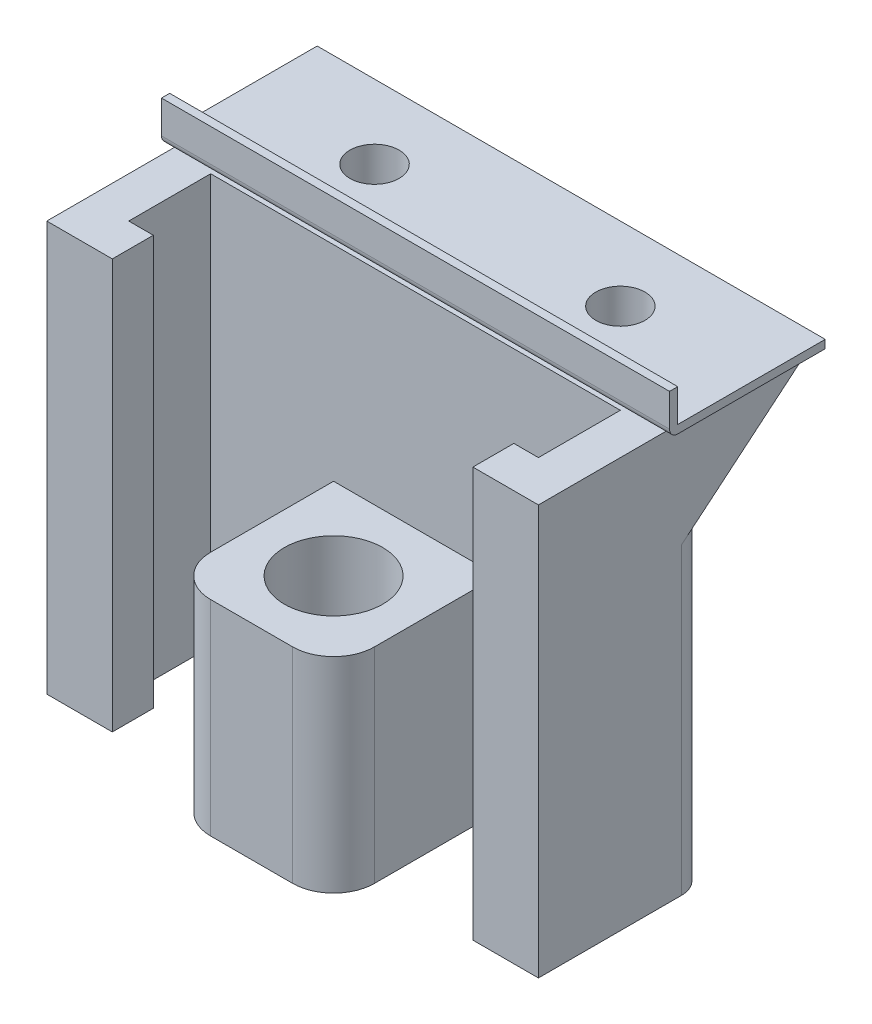
SolidWorks part; units mm, degrees
note: The reader was unsure of these and kept them because the rebuilt part matched: shared geometry of "草图9<8>".
material "1060 合金"
ref_plane "前视基准面" through (0, 0, 0) normal (0, 0, 1) x (1, 0, 0)
ref_plane "上视基准面" through (0, 0, 0) normal (0, 1, 0) x (1, 0, 0)
ref_plane "右视基准面" through (0, 0, 0) normal (1, 0, 0) x (0, 0, -1)
sketch "草图2" plane through (0, 0, 0) normal (0, 1, 0) x (1, 0, 0)
  line L0 (30, -7.5) -> (-30, -7.5)
  line L1 (30, 12.5) -> (-30, 12.5)
  line L2 (30, 12.5) -> (30, -12.5)
  line L3 (30, -12.5) -> (-30, -12.5)
  line L4 (-30, 12.5) -> (-30, -12.5)
  line L5 (30, 12.5) -> (-30, -12.5) construction
  line L6 (30, -12.5) -> (-30, 12.5) construction
  line L7 (-25, 12.5) -> (25, 12.5)
  line L8 (-25, 12.5) -> (-25, -12.5)
  line L9 (-25, -12.5) -> (25, -12.5)
  line L10 (25, 12.5) -> (25, -12.5)
  line L11 (-25, 12.5) -> (25, -12.5) construction
  line L12 (-25, -12.5) -> (25, 12.5) construction
  line L13 (-22, -7.5) -> (-22, -12.5)
  line L14 (0, -12.5) -> (0, 0) construction
  line L15 (22, -7.5) -> (22, -12.5)
  line L16 (-25, 2.5) -> (30, 2.5)
  circle A0 centre (-30, 12.5) radius 5
  circle A1 centre (30, 12.5) radius 5.0923
  point P0 (0, 0)
  point P6 (0, 0)
  dimension "D1" = 60
  dimension "D2" = 25
  dimension "D3" = 50
  dimension "D4" = 5
  dimension "D5" = 3
  dimension "D6" = 10
extrude "凸台-拉伸1" add sketch "草图2" along normal blind 50 contours L0 L10 L3 L2 | L0 L15 L3 L10 | L16 L10 L0 L2 | L10 L16 L2 L1 | L8 L16 L10 L1 | L8 L1 L4 L0 | L8 L0 L4 L3 | L13 L0 L8 L9
fillet "圆角3" radius 3 2 edges at (-30, 25, -7.5) (-25, 25, -12.5)
fillet "圆角4" radius 3 2 edges at (24.9077, 25, -12.5) (30, 25, -7.4077)
ref_plane "基准面1" through (0, 50, 0) normal (0, 1, 0) x (1, 0, 0)
sketch "草图3" plane through (0, 50, 0) normal (0, 1, 0) x (1, 0, 0)
  line L1 (-25, 2.5) -> (-30, 2.5)
  line L2 (-25, 2.5) -> (-25, 19.5)
  line L3 (-25, 19.5) -> (-30, 19.5)
  line L4 (-30, 2.5) -> (-30, 19.5)
  dimension "D1" = 17
ref_plane "基准面2" through (-30, 0, 0) normal (-1, 0, 0) x (0, 0, 1)
sketch "草图5" plane through (-30, 0, 0) normal (-1, 0, 0) x (0, 0, 1)
  line L0 (-2.5, 50) -> (-20.5, 50)
  line L3 (26.0511, 50) -> (-26.0511, 50) construction
  line L4 (-20.5, 50) -> (-2.5, 35)
  line L5 (-2.5, 35) -> (-2.5, 50)
  dimension "D1" = 18
  dimension "D2" = 15
extrude "凸台-拉伸4" add sketch "草图5" against normal blind 60
ref_plane "基准面3" through (-31, 0, 0) normal (-1, 0, 0) x (0, 0, 1)
sketch "草图7" plane through (-31, 0, 0) normal (-1, 0, 0) x (0, 0, 1)
  line L0 (-2.5, 51.5916) -> (-2.5, 50)
  line L1 (-2.5, 50) -> (-19.5, 50) construction
  line L2 (-2.5, 50) -> (-21.5, 50)
  line L3 (26.0511, 50) -> (-26.0511, 50) construction
  line L4 (-21.5, 50) -> (-21.5, 51)
  line L5 (-21.5, 51) -> (-3.5, 51)
  line L6 (-3.5, 51) -> (-3.5, 55)
  line L7 (-3.5, 55) -> (-2.5, 55)
  line L8 (-2.5, 51.5916) -> (-2.5, 55)
  line L13 (-2.5, 50) -> (12.5, 50)
  circle A0 centre (-3.5, 51) radius 1
  dimension "D1" = 1
  dimension "D2" = 1
  dimension "D3" = 18
  dimension "D4" = 4
  dimension "D5" = 15
  dimension "D6" = 0
extrude "凸台-拉伸5" add sketch "草图7" against normal blind 62 contours A0 L0 L8 L7 L6 | A0 L6 L5 | A0 L5 L4 L2
sketch "草图8" plane through (0, 50, 0) normal (0, 1, 0) x (1, 0, 0)
  line L0 (0, 21.5) -> (0, 3.5)
  line L1 (31, 21.5) -> (-31, 21.5)
  line L2 (31, 21.5) -> (31, 3.5)
  line L3 (31, 3.5) -> (-31, 3.5)
  line L4 (-31, 21.5) -> (-31, 3.5)
  line L5 (0, 12.5) -> (-31, 12.5)
  line L6 (0, 12.5) -> (-15, 12.5)
  circle A0 centre (-15, 12.5) radius 3
  circle A1 centre (15, 12.5) radius 3
  dimension "D1" = 62
  dimension "D2" = 18
  dimension "D3" = 15
extrude "切除-拉伸7" cut sketch "草图8" against normal blind 4 and the other way through all contours A0 | A1
sketch "草图9" plane through (0, 0, 0) normal (0, 1, 0) x (1, 0, 0)
  line L0 (0, -14.3601) -> (0, 21.5)
  line L1 (31, 21.5) -> (-31, 21.5) construction
  line L2 (31, 2.5) -> (-31, 2.5) construction
  line L3 (10, 2.5) -> (-10, 2.5)
  line L4 (0, 2.5) -> (0, -17.5)
  line L5 (5, -17.5) -> (-5, -17.5)
  line L6 (-10, 2.5) -> (-10, -12.5)
  line L7 (10, 2.5) -> (10, -12.5)
  line L8 (0, 2.5) -> (0, -7.5)
  circle A0 centre (0, -7.5) radius 6
  arc A1 (10, -12.5) -> (5, -17.5) centre (5, -12.5) cw
  arc A2 (-5, -17.5) -> (-10, -12.5) centre (-5, -12.5) cw
  point P16 (10, -17.5)
  point P19 (-10, -17.5)
  dimension "D4" = 5
  dimension "D1" = 10
  dimension "D2" = 20
  dimension "D3" = 10
extrude "凸台-拉伸6" add sketch "草图9" along normal blind 25 contours A2 L5 L4 L0 A0 L8 L3 L6 | A1 L7 L3 L8 A0 L0 L4 L5
extrude "切除-拉伸10" cut sketch "草图9<8>" against normal blind 10 and the other way through all contours L4 A0 | L4 A0
sketch "草图9<8>" plane through (0, 0, 0) normal (0, 1, 0) x (1, 0, 0) same geometry as "草图9"
